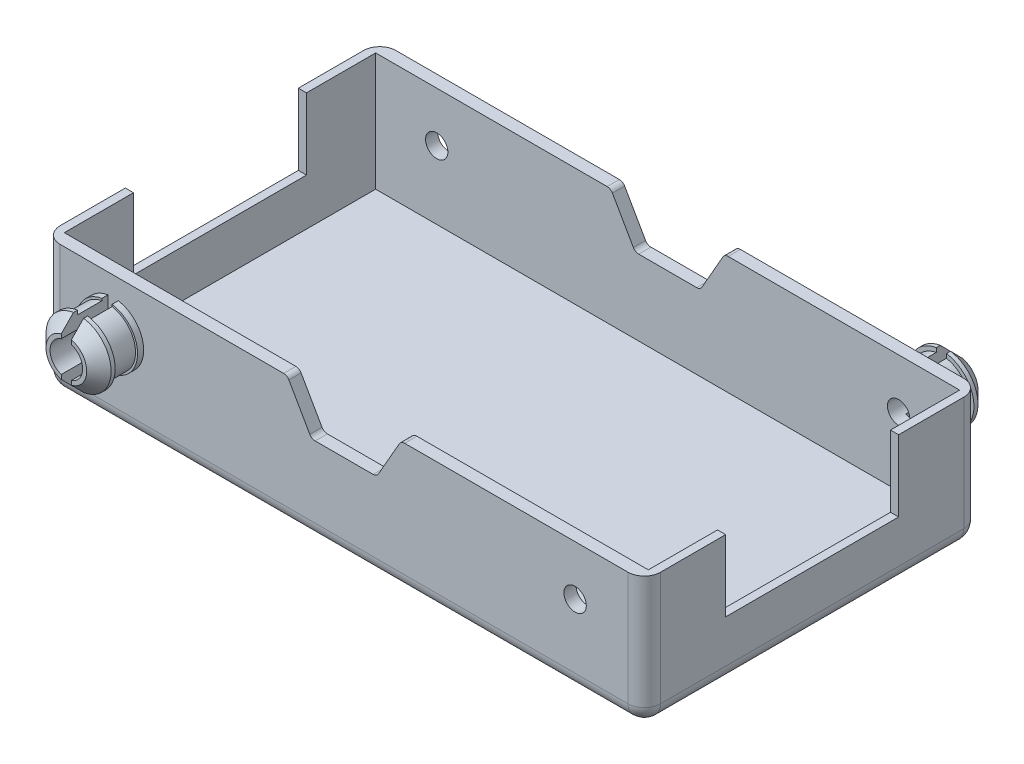
SolidWorks part; units mm, degrees
ref_plane "Front Plane" through (0, 0, 0) normal (0, 0, 1) x (1, 0, 0)
ref_plane "Top Plane" through (0, 0, 0) normal (0, 1, 0) x (1, 0, 0)
ref_plane "Right Plane" through (0, 0, 0) normal (1, 0, 0) x (0, 0, -1)
sketch "Sketch1" plane through (0, 0, 0) normal (0, 1, 0) x (1, 0, 0)
  line L1 (0, 0) -> (147.5, 0)
  line L2 (0, 0) -> (0, 82.5)
  line L3 (0, 82.5) -> (147.5, 82.5)
  line L4 (147.5, 0) -> (147.5, 82.5)
  dimension "D1" = 147.5
  dimension "D2" = 82.5
extrude "Boss-Extrude1" add sketch "Sketch1" along normal blind 32
shell "Shell1" thickness 3 removed face at (73.75, 32, -41.25)
fillet "Fillet1" radius 4 8 edges at (73.75, 0, 0) (147.5, 0, -41.25) (73.75, 0, -82.5) (0, 0, -41.25) (147.5, 16, -82.5) (147.5, 16, 0) (0, 16, -82.5) (0, 16, 0)
sketch "Sketch4" plane through (3, 0, 0) normal (1, 0, 0) x (0, 0, -1)
  line L4 (3, 3) -> (79.5, 3)
  line L5 (79.5, 3) -> (79.5, 32)
  line L6 (79.5, 32) -> (3, 32)
  line L7 (79.5, 3) -> (79.5, 32)
  line L8 (3, 3) -> (79.5, 3)
  line L10 (79.5, 32) -> (3, 32)
  line L12 (3, 32) -> (3, 3)
  line L13 (3, 32) -> (3, 3)
  dimension "D1" = 0
extrude "Cut-Extrude1" cut sketch "Sketch4" along normal offset from surface (143.5 mm away) 2 from offset 1 up to face at (147.5, 18, -41.25) offset against normal yes
sketch "Sketch5" plane through (147.5, 0, 0) normal (1, 0, 0) x (0, 0, -1)
  line L0 (4, 32) -> (78.5, 32) construction
  line L1 (20, 32) -> (62.5, 32)
  line L2 (20, 32) -> (20, 14.5)
  line L3 (20, 14.5) -> (62.5, 14.5)
  line L4 (62.5, 32) -> (62.5, 14.5)
  line L6 (78.5, 0) -> (4, 0) construction
  line L7 (41.25, 4) -> (41.25, 46.3808) construction
  line L8 (4, 4) -> (78.5, 4) construction
  point P12 (41.25, 14.5)
  dimension "D1" = 42.5
  dimension "D2" = 14.5
extrude "Cut-Extrude2" cut sketch "Sketch5" against normal up to surface (147.5 mm away) up to face at (0, 18, -41.25)
sketch "Sketch6" plane through (0, 0, 0) normal (0, 0, 1) x (1, 0, 0)
  line L0 (4, 32) -> (143.5, 32) construction
  line L1 (65.75, 21.5) -> (81.75, 21.5)
  line L4 (81.75, 21.5) -> (81.75, 32) construction
  line L5 (65.75, 21.5) -> (73.75, 32) construction
  line L6 (73.75, 32) -> (81.75, 21.5) construction
  line L7 (81.75, 21.5) -> (87.75, 32)
  line L8 (65.75, 21.5) -> (59.75, 32)
  line L9 (59.75, 32) -> (87.75, 32)
  point P0 (73.75, 32)
  dimension "D1" = 8
  dimension "D2" = 14
  dimension "D3" = 14
  dimension "D4" = 10.5
extrude "Cut-Extrude3" cut sketch "Sketch6" against normal up to surface (82.5 mm away) up to face at (73.75, 18, -82.5)
fillet "Fillet2" radius 1.5 8 edges at (87.75, 32, -81) (81.75, 21.5, -81) (59.75, 32, -81) (65.75, 21.5, -81) (87.75, 32, -1.5) (81.75, 21.5, -1.5) (59.75, 32, -1.5) (65.75, 21.5, -1.5)
sketch "Sketch7" plane through (0, 0, 0) normal (0, 0, 1) x (1, 0, 0)
  line L0 (143.5, 4) -> (143.5, 32) construction
  line L1 (4, 4) -> (143.5, 4) construction
  line L2 (4, 32) -> (4, 4) construction
  line L3 (73.75, 4) -> (73.75, 37.0086) construction
  circle A0 centre (17, 19.75) radius 2.75
  circle A2 centre (130.5, 19.75) radius 2.75
  point P2 (17, 17)
  dimension "D1" = 5.5
  dimension "D3" = 13
  dimension "D2" = 13
  dimension "D4" = 13
extrude "Cut-Extrude4" cut sketch "Sketch7" against normal up to surface (82.5 mm away) up to face at (73.75, 23.8333, -82.5)
sketch "Sketch8" plane through (0, 0, 0) normal (0, 0, 1) x (1, 0, 0)
  line L0 (17, 19.75) -> (17, 30.7129) construction
  line L1 (15.75, 32) -> (15.75, 0) construction
  line L2 (4, 32) -> (58.8795, 32) construction
  line L3 (143.5, 0) -> (4, 0) construction
  line L4 (18.25, 32) -> (18.25, 0) construction
  circle A0 centre (17, 19.75) radius 8
  circle A2 centre (17, 19.75) radius 6
  circle A4 centre (17, 19.75) radius 5
  dimension "D1" = 16
  dimension "D2" = 3
  dimension "D3" = 1
  dimension "D4" = 1.25
  dimension "D5" = 2.5
sketch "Sketch9" plane through (0, 0, 0) normal (0, 0, 1) x (1, 0, 0)
  circle A0 centre (17, 19.75) radius 7.5
  circle A1 centre (17, 19.75) radius 2.75 construction
  circle A2 centre (17, 19.75) radius 2.75
  dimension "D1" = 15
extrude "Boss-Extrude3" add sketch "Sketch9" along normal blind 1.5
ref_axis "Axis1" through (17, 19.75, 0) along (0, 0, 1)
ref_plane "Plane1" through (17, 0, 0) normal (-1, 0, 0) x (0, 0, 1)
sketch "Sketch10" plane through (17, 0, 0) normal (-1, 0, 0) x (0, 0, 1)
  line L0 (0, 19.75) -> (33.8718, 19.75) construction
  line L1 (0, 32) -> (0, 0) construction
  line L2 (0, 19.75) -> (54.7881, 19.75) construction
  line L4 (11.5, 24.75) -> (8.5, 27.75)
  line L5 (8.5, 27.75) -> (7.5, 27.75)
  line L6 (7.5, 27.75) -> (7.5, 26.75)
  line L10 (1.5, 23.75) -> (11.5, 23.75)
  line L11 (11.5, 24.75) -> (11.5, 29.847) construction
  line L12 (8.5, 27.75) -> (15.1697, 21.0803) construction
  line L13 (11.5, 24.75) -> (11.5, 23.75)
  line L14 (7.5, 26.75) -> (1.5, 26.75)
  line L15 (1.5, 12.25) -> (1.5, 27.25) construction
  line L16 (1.5, 26.75) -> (1.5, 23.75)
  dimension "D1" = 1
  dimension "D2" = 1
  dimension "D3" = 4
  dimension "D4" = 135
  dimension "D5" = 1
  dimension "D6" = 8
  dimension "D7" = 10
revolve "Revolve1" add sketch "Sketch10" angle 360 about axis through (17, 19.75, 0) along (0, 0, 1)
sketch "Sketch11" plane through (0, 0, 0) normal (0, 0, 1) x (1, 0, 0)
  line L2 (15.75, 32) -> (15.75, 0) construction
  line L3 (15.75, 27.75) -> (18.25, 27.75)
  line L4 (18.25, 32) -> (18.25, 0) construction
  line L5 (18.25, 27.75) -> (18.25, 11.75)
  line L6 (18.25, 11.75) -> (15.75, 11.75)
  line L7 (15.75, 11.75) -> (15.75, 27.75)
extrude "Cut-Extrude5" cut sketch "Sketch11" along normal up to surface (11.5 mm away) up to face at (12, 19.75, 11.5)
ref_plane "Plane2" through (73.75, 0, 0) normal (-1, 0, 0) x (0, 0, 1)
ref_plane "Plane3" through (0, 0, -41.25) normal (0, 0, 1) x (1, 0, 0)
ref_plane "Plane4" through (57.5, 0, -57.5) normal (-0.7071, 0, 0.7071) x (0.7071, 0, 0.7071)
mirror "Mirror2" about plane through (73.75, 0, 0) normal (-1, 0, 0) of "Cut-Extrude5", "Revolve1", "Boss-Extrude3" second plane through (0, 0, -41.25) second plane normal (0, 0, 1)
sketch "Sketch12" plane through (0, 0, -82.5) normal (0, 0, -1) x (-1, 0, 0)
  line L0 (-4, 4) -> (-4, 32) construction
  line L1 (-29.2385, 30.4129) -> (-4, 30.4129)
  line L2 (-29.2385, 30.4129) -> (-29.2385, 7.9541)
  line L3 (-29.2385, 7.9541) -> (-4, 7.9541)
  line L4 (-4, 30.4129) -> (-4, 7.9541)
extrude "Cut-Extrude6" cut sketch "Sketch12" along normal up to surface (11.5 mm away) up to face at (14.125, 19.75, -94)
sketch "Sketch13" plane through (0, 0, 0) normal (0, 0, 1) x (1, 0, 0)
  line L0 (143.5, 4) -> (143.5, 32) construction
  line L1 (61.9909, 29.7891) -> (143.5, 29.7891)
  line L2 (61.9909, 29.7891) -> (61.9909, 10.4496)
  line L3 (61.9909, 10.4496) -> (143.5, 10.4496)
  line L4 (143.5, 29.7891) -> (143.5, 10.4496)
extrude "Cut-Extrude7" cut sketch "Sketch13" along normal up to surface (11.5 mm away)
